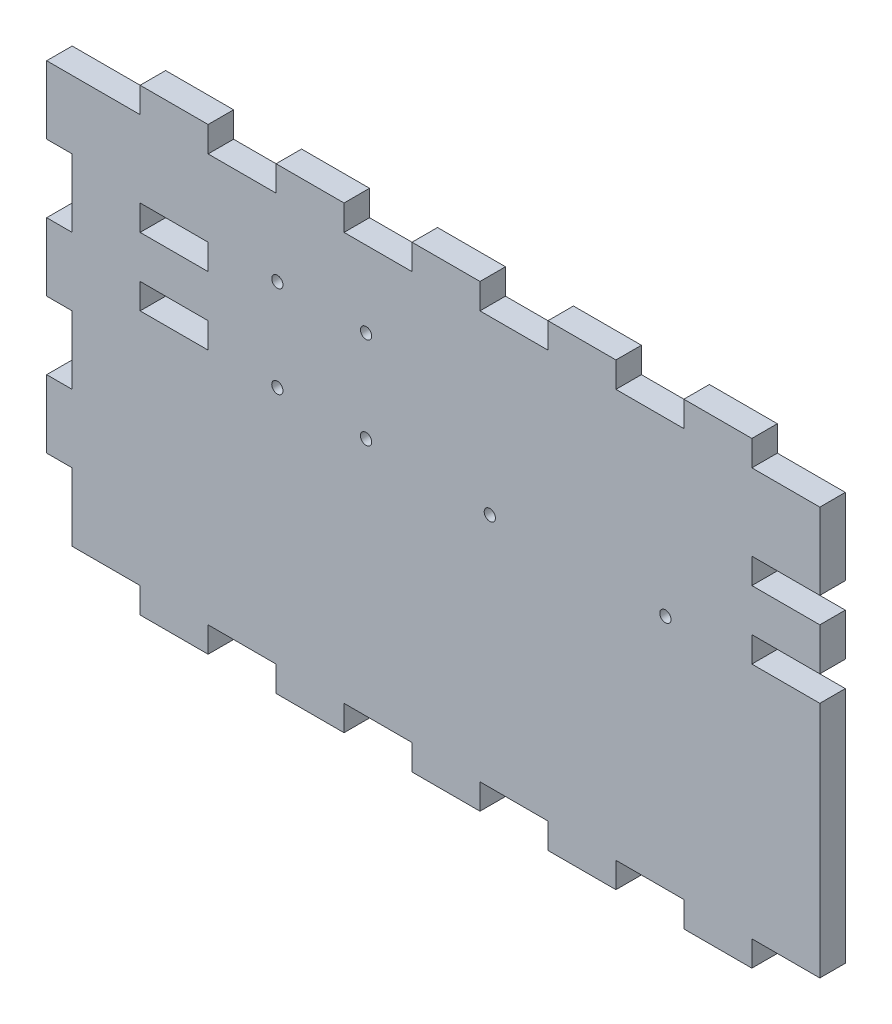
SolidWorks part; units mm, degrees
ref_plane "Front Plane" through (0, 0, 0) normal (0, 0, 1) x (1, 0, 0)
ref_plane "Top Plane" through (0, 0, 0) normal (0, 1, 0) x (1, 0, 0)
ref_plane "Right Plane" through (0, 0, 0) normal (1, 0, 0) x (0, 0, -1)
sketch "Sketch1" plane through (0, 0, 0) normal (0, 0, 1) x (1, 0, 0)
  line L1 (-139.7, -76.2) -> (139.7, -76.2)
  line L2 (-139.7, -76.2) -> (-139.7, 76.2)
  line L3 (-139.7, 76.2) -> (139.7, 76.2)
  line L4 (139.7, -76.2) -> (139.7, 76.2)
  line L5 (-139.7, -76.2) -> (139.7, 76.2) construction
  line L6 (-139.7, 76.2) -> (139.7, -76.2) construction
  point P0 (0, 0)
  dimension "D1" = 279.4
  dimension "D2" = 152.4
extrude "Boss-Extrude1" add sketch "Sketch1" along normal blind 9.525
sketch "Sketch2" plane through (0, -76.2, 0) normal (0, -1, 0) x (1, 0, 0)
  line L0 (-139.7, 0) -> (139.7, 0) construction
  line L1 (-114.3, 0) -> (-88.9, 0)
  line L2 (-114.3, 0) -> (-114.3, 9.525)
  line L3 (-114.3, 9.525) -> (-88.9, 9.525)
  line L4 (-88.9, 0) -> (-88.9, 9.525)
  line L5 (-139.7, 9.525) -> (139.7, 9.525) construction
  line L6 (-139.7, 9.525) -> (-139.7, 0) construction
  point P10 (-139.7, 4.7625)
  dimension "D1" = 25.4
  dimension "D2" = 25.4
extrude "Boss-Extrude2" add sketch "Sketch2" along normal blind 9.525
pattern_linear "LPattern1" count 5 spacing 50.8 along (1, 0, 0) of "Boss-Extrude2"
mirror "Mirror1" about plane through (0, 0, 0) normal (0, 1, 0) of "LPattern1"
sketch "Sketch3" plane through (-139.7, 0, 0) normal (-1, 0, 0) x (0, 0, 1)
  line L0 (0, 76.2) -> (0, -76.2) construction
  line L1 (9.525, 76.2) -> (0, 76.2)
  line L2 (9.525, 76.2) -> (9.525, 50.8)
  line L3 (9.525, 50.8) -> (0, 50.8)
  line L4 (0, 76.2) -> (0, 50.8)
  dimension "D1" = 25.4
extrude "Boss-Extrude3" add sketch "Sketch3" along normal blind 9.525
pattern_linear "LPattern2" count 3 spacing 50.8 along (0, -1, 0) of "Boss-Extrude3"
sketch "Sketch4" plane through (0, 0, 0) normal (0, 0, -1) x (-1, 0, 0)
  line L1 (-139.7, 12.7) -> (-114.3, 12.7)
  line L2 (-139.7, 12.7) -> (-139.7, 22.225)
  line L3 (-139.7, 22.225) -> (-114.3, 22.225)
  line L4 (-114.3, 12.7) -> (-114.3, 22.225)
  line L5 (-114.3, -76.2) -> (-139.7, -76.2) construction
  line L6 (-139.7, -76.2) -> (-139.7, 76.2) construction
  dimension "D1" = 25.4
  dimension "D2" = 9.525
  dimension "D4" = 88.9
extrude "Cut-Extrude1" cut sketch "Sketch4" against normal through all
pattern_linear "LPattern3" count 2 spacing 228.6 along (-1, 0, 0) of "Cut-Extrude1"
sketch "Sketch5" plane through (0, 0, 9.525) normal (0, 0, 1) x (1, 0, 0)
  line L1 (-88.9, 47.625) -> (-114.3, 47.625)
  line L2 (-88.9, 47.625) -> (-88.9, 38.1)
  line L3 (-88.9, 38.1) -> (-114.3, 38.1)
  line L4 (-114.3, 47.625) -> (-114.3, 38.1)
  line L5 (-88.9, -76.2) -> (-63.5, -76.2) construction
  line L8 (-114.3, 12.7) -> (-114.3, 22.225) construction
  dimension "D1" = 25.4
  dimension "D2" = 9.525
  dimension "D3" = 114.3
extrude "Cut-Extrude2" cut sketch "Sketch5" against normal through all
pattern_linear "LPattern4" count 2 spacing 228.6 along (1, 0, 0) of "Cut-Extrude2"
sketch "Sketch6" plane through (0, 0, 0) normal (0, 0, -1) x (-1, 0, 0)
  circle A0 centre (-81.9861, 12) radius 2.1 construction
  circle A1 centre (-81.9861, 12) radius 2.1
  circle A2 centre (-16.3789, 12) radius 2.1 construction
  circle A3 centre (-16.3789, 12) radius 2.1
  circle A4 centre (63.02, 13.5088) radius 2.1 construction
  circle A5 centre (63.02, 13.5088) radius 2.1
  circle A6 centre (29.87, 47.77) radius 2.1 construction
  circle A7 centre (29.87, 47.77) radius 2.1
  circle A8 centre (63.02, 47.77) radius 2.1 construction
  circle A9 centre (63.02, 47.77) radius 2.1
  circle A10 centre (29.87, 13.5088) radius 2.1 construction
  circle A11 centre (29.87, 13.5088) radius 2.1
extrude "Cut-Extrude3" cut sketch "Sketch6" against normal through all
